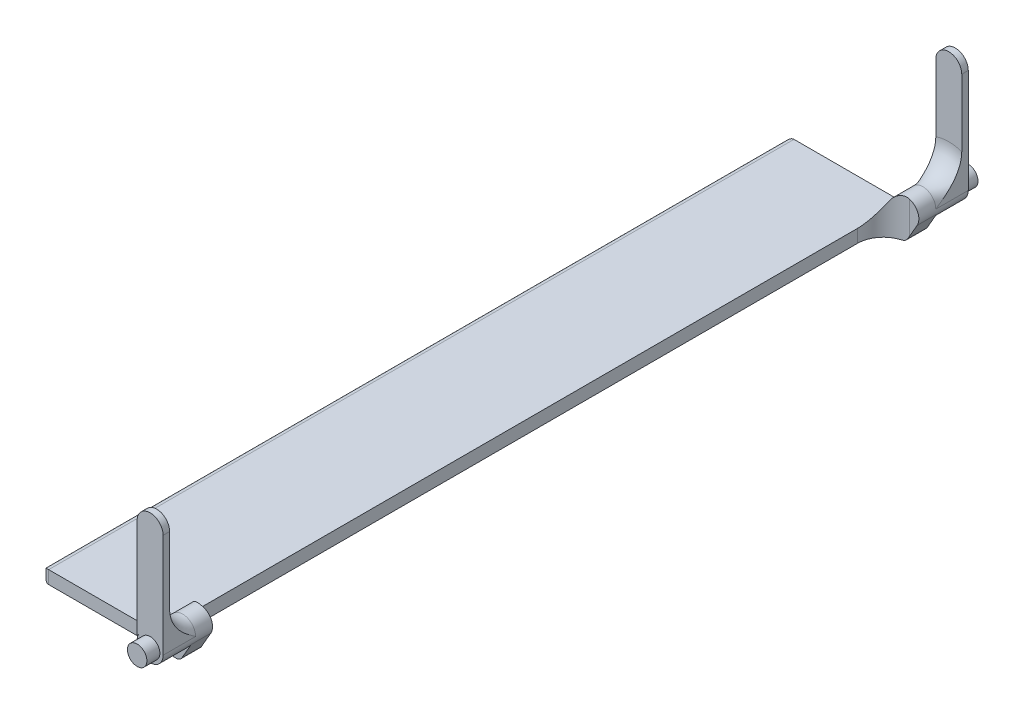
SolidWorks part; units mm, degrees
material "ABS"
ref_plane "Front Plane" through (0, 0, 0) normal (0, 0, 1) x (1, 0, 0)
ref_plane "Top Plane" through (0, 0, 0) normal (0, 1, 0) x (1, 0, 0)
ref_plane "Right Plane" through (0, 0, 0) normal (1, 0, 0) x (0, 0, -1)
sketch "Sketch1" plane through (0, 0, 0) normal (0, 0, 1) x (1, 0, 0)
  line B0 (-33.7058, -6.35) -> (-33.7058, -3.175)
  line B1 (-33.7058, -6.35) -> (0, -6.35)
  line B2 (0, -6.35) -> (2.7496, -1.5875)
  line B3 (-33.7058, -3.175) -> (-5.4993, -3.175)
  line B4 (-2.7496, 1.5875) -> (-5.4993, -3.175)
  circle B5 centre (0, 0) radius 2.3812
  circle B6 centre (0, 0) radius 3.175
sketch_block_instance "trap_door_geometry-1"
sketch_block "trap_door_geometry" parameters "D1"=4.7625, "D2"=6.35
extrude "Boss-Extrude1" add sketch "Sketch1" along normal mid plane 182.2196 contours B6 B4 B3 B0 B1 B2 | B6 B5 | B5 region at (-15.5478, -4.5785, 0) region at (-1.5426, -2.6719, 0) region at (0, 0, 0)
sketch "Sketch2" plane through (0, 0, 0) normal (0, 1, 0) x (1, 0, 0)
  line L0 (-5.4993, -91.1098) -> (-5.4993, 91.1098) construction
  line L1 (3.175, -91.1098) -> (3.175, 91.1098) construction
  line L2 (-5.4993, -91.1098) -> (-5.4993, 91.1098)
  line L3 (3.175, -91.1098) -> (3.175, 91.1098)
  line L4 (3.175, -86.3473) -> (-5.4993, -86.3473)
  line L5 (-2.7496, -91.1098) -> (3.175, -91.1098) construction
  line L6 (0, 0) -> (50000, 0) construction
  line L7 (3.175, 86.3473) -> (-5.4993, 86.3473)
  dimension "D1" = 4.7625
extrude "Cut-Extrude1" cut sketch "Sketch2" against normal through all both and the other way through all contours L2 L6 L3 L7 | L6 L2 L4 L3 region at (-1.1621, 0, 0)
fillet "Fillet1" radius 1.5875 6 edges at (0, -6.35, -88.7285) (0, -6.35, 88.7285) (-33.7058, -4.7625, 91.1098) (-33.7058, -6.35, 0) (-33.7058, -3.175, 0) (-33.7058, -4.7625, -91.1098)
sketch "Sketch3" plane through (0, 0, 91.1098) normal (0, 0, 1) x (1, 0, 0)
  circle A0 centre (0, 0) radius 3.175
  dimension "D1" = 6.35
extrude "Boss-Extrude2" add sketch "Sketch3" along normal blind 7.3152
sketch "Sketch4" plane through (0, 0, 98.425) normal (0, 0, 1) x (1, 0, 0)
  circle A0 centre (0, 0) radius 2.3813
  dimension "D1" = 4.7625
extrude "Boss-Extrude3" add sketch "Sketch4" along normal blind 3.175
mirror "Mirror1" about plane through (0, 0, 0) normal (0, 0, 1) of "Boss-Extrude2", "Boss-Extrude3"
sketch "Sketch6" plane through (0, 0, -98.425) normal (0, 0, -1) x (-1, 0, 0)
  line L0 (0, 0) -> (0, 50000) construction
  line L1 (2.7496, 1.5875) -> (5.4993, -3.175) construction
  line L2 (2.7496, 1.5875) -> (3.175, 0.8507)
  line L3 (-3.175, 25.4) -> (-3.175, 0)
  line L4 (3.175, 25.4) -> (3.175, 0.8507)
  circle A0 centre (0, 0) radius 3.175 construction
  arc A1 (2.7496, 1.5875) -> (-3.175, 0) centre (0, 0) ccw
  arc A2 (3.175, 25.4) -> (-3.175, 25.4) centre (0, 25.4) ccw
  dimension "D1" = 6.35
  dimension "D2" = 25.4
extrude "Boss-Extrude4" add sketch "Sketch6" against normal blind 1.5875
mirror "Mirror2" about plane through (0, 0, 0) normal (0, 0, 1) of "Boss-Extrude4"
fillet "Fillet2" radius 6.35 2 edges at (-5.4993, -4.7625, 86.3473) (-5.4993, -4.7625, -86.3473)
fillet "Fillet4" radius 6.35 2 edges at (0.8218, 3.0668, 96.8375) (0.8218, 3.0668, -96.8375)
